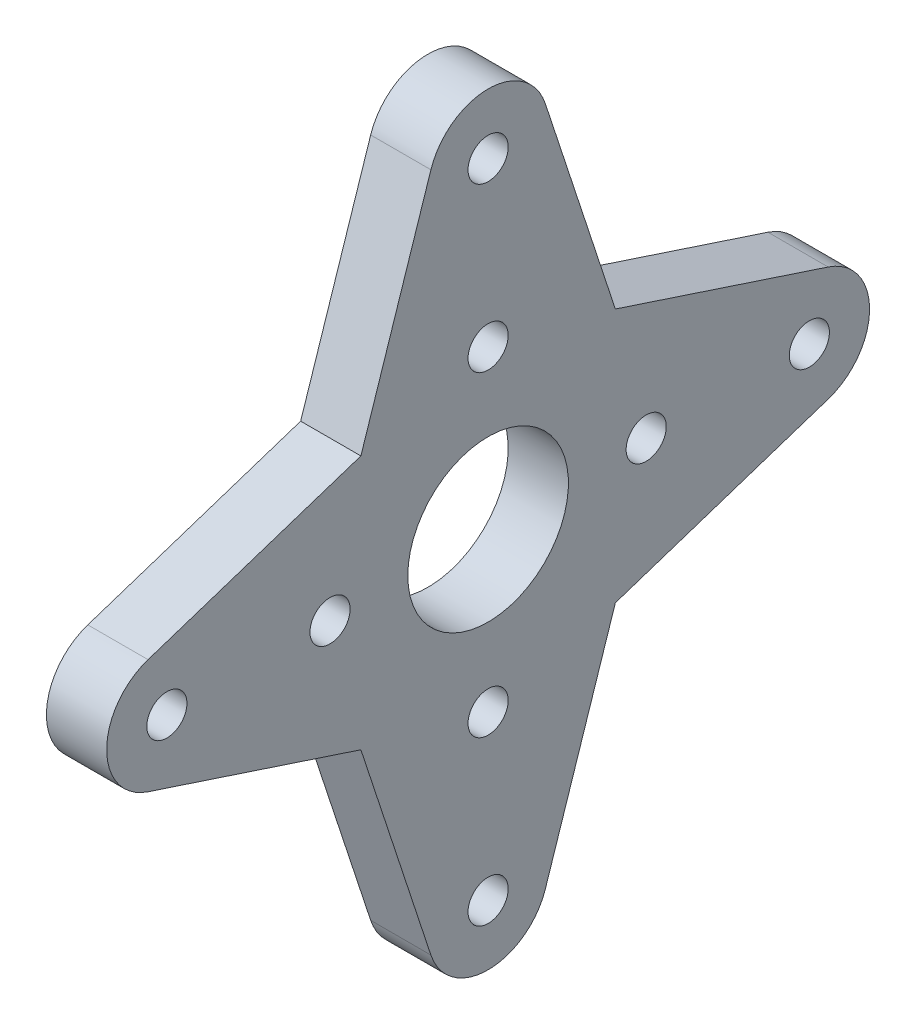
SolidWorks part; units mm, degrees
ref_plane "Front Plane" through (0, 0, 0) normal (0, 0, 1) x (1, 0, 0)
ref_plane "Top Plane" through (0, 0, 0) normal (0, 1, 0) x (1, 0, 0)
ref_plane "Right Plane" through (0, 0, 0) normal (1, 0, 0) x (0, 0, -1)
sketch "Sketch1" plane through (0, 0, 0) normal (1, 0, 0) x (0, 0, -1)
  line L0 (4.524, 26.8883) -> (10.0601, 10.0601)
  line L1 (0, 25.4) -> (0, 0) construction
  line L2 (-4.524, 26.8883) -> (-10.0601, 10.0601)
  line L3 (26.8883, 4.524) -> (10.0601, 10.0601)
  line L4 (26.8883, -4.524) -> (10.0601, -10.0601)
  line L5 (4.524, -26.8883) -> (10.0601, -10.0601)
  line L6 (-4.524, -26.8883) -> (-10.0601, -10.0601)
  line L7 (-26.8883, -4.524) -> (-10.0601, -10.0601)
  line L8 (-26.8883, 4.524) -> (-10.0601, 10.0601)
  circle A0 centre (0, 0) radius 6.35
  circle A1 centre (0, 25.4) radius 1.5875
  circle A2 centre (0, 12.5) radius 1.5875
  arc A3 (4.524, 26.8883) -> (-4.524, 26.8883) centre (0, 25.4) ccw
  circle A5 centre (12.5, 0) radius 1.5875
  circle A6 centre (25.4, 0) radius 1.5875
  arc A7 (26.8883, -4.524) -> (26.8883, 4.524) centre (25.4, 0) ccw
  circle A8 centre (0, -12.5) radius 1.5875
  circle A9 centre (0, -25.4) radius 1.5875
  arc A10 (-4.524, -26.8883) -> (4.524, -26.8883) centre (0, -25.4) ccw
  circle A11 centre (-12.5, 0) radius 1.5875
  circle A12 centre (-25.4, 0) radius 1.5875
  arc A13 (-26.8883, 4.524) -> (-26.8883, -4.524) centre (-25.4, 0) ccw
  dimension "D1" = 9.525
  dimension "D3" = 3.175
  dimension "D5" = 3.175
  dimension "D6" = 25.4
  dimension "D7" = 4
  dimension "D2" = 12.5
extrude "Boss-Extrude1" add sketch "Sketch1" along normal blind 4.7625 contours A1 A2 A0 A5 A8 A9 A11 A12 region at (0, 18.2076, -6.4816)
